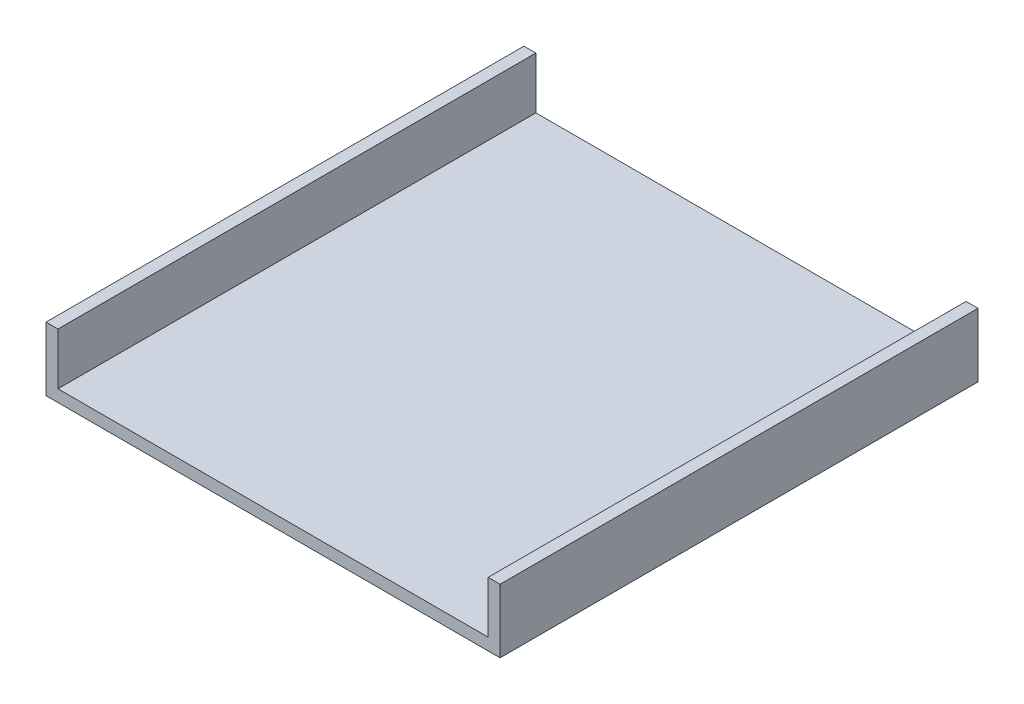
SolidWorks part; units mm, degrees
ref_plane "Front Plane" through (0, 0, 0) normal (0, 0, 1) x (1, 0, 0)
ref_plane "Top Plane" through (0, 0, 0) normal (0, 1, 0) x (1, 0, 0)
ref_plane "Right Plane" through (0, 0, 0) normal (1, 0, 0) x (0, 0, -1)
sketch "Sketch1" plane through (0, 0, 0) normal (0, 0, 1) x (1, 0, 0)
  line L1 (57, -8) -> (-57, -8)
  line L2 (57, -8) -> (57, 8)
  line L3 (57, 8) -> (-57, 8)
  line L4 (-57, -8) -> (-57, 8)
  line L5 (57, -8) -> (-57, 8) construction
  line L6 (57, 8) -> (-57, -8) construction
  point P0 (0, 0)
  dimension "D1" = 114
  dimension "D2" = 16
extrude "Boss-Extrude1" add sketch "Sketch1" along normal blind 60 and the other way blind 60
sketch "Sketch2" plane through (0, 0, 60) normal (0, 0, 1) x (1, 0, 0)
  line L0 (57, 8) -> (-57, 8) construction
  line L1 (-54, 21) -> (54, 21)
  line L2 (-54, 21) -> (-54, -5)
  line L3 (-54, -5) -> (54, -5)
  line L4 (54, 21) -> (54, -5)
  line L5 (-54, 21) -> (54, -5) construction
  line L6 (-54, -5) -> (54, 21) construction
  line L7 (57, -8) -> (57, 8) construction
  line L8 (-57, -8) -> (57, -8) construction
  point P0 (0, 8)
  dimension "D1" = 3
  dimension "D2" = 3
extrude "Cut-Extrude1" cut sketch "Sketch2" against normal through all
